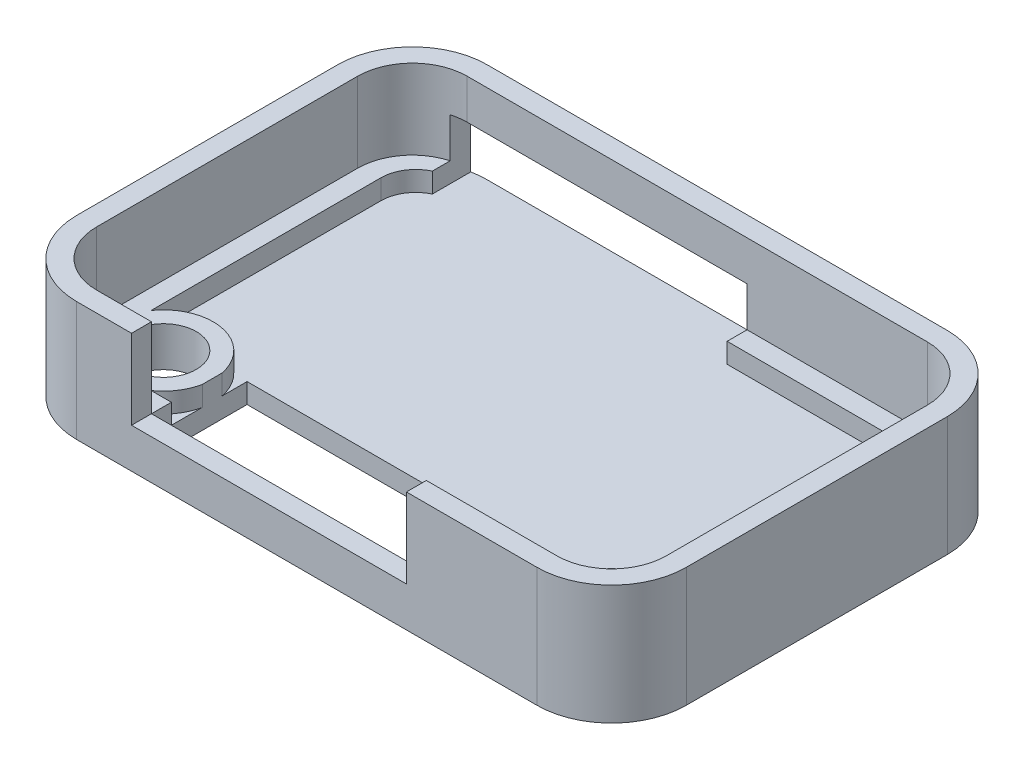
SolidWorks part; units mm, degrees
ref_plane "前视基准面" through (0, 0, 0) normal (0, 0, 1) x (1, 0, 0)
ref_plane "上视基准面" through (0, 0, 0) normal (0, 1, 0) x (1, 0, 0)
ref_plane "右视基准面" through (0, 0, 0) normal (1, 0, 0) x (0, 0, -1)
other "Configuration Table"
sketch "草图1" plane through (0, 0, 0) normal (0, 1, 0) x (1, 0, 0)
  line L1 (-15.3, 10.3) -> (15.3, 10.3)
  line L2 (-15.3, 10.3) -> (-15.3, -10.3)
  line L3 (-15.3, -10.3) -> (15.3, -10.3)
  line L4 (15.3, 10.3) -> (15.3, -10.3)
extrude "凸台-拉伸1" add sketch "草图1" along normal blind 6
sketch "草图2" plane through (0, 6, 0) normal (0, 1, 0) x (1, 0, 0)
  line L1 (-14.3, 9.3) -> (14.3, 9.3)
  line L2 (-14.3, 9.3) -> (-14.3, -9.3)
  line L3 (-14.3, -9.3) -> (14.3, -9.3)
  line L4 (14.3, 9.3) -> (14.3, -9.3)
extrude "切除-拉伸1" cut sketch "草图2" against normal blind 4
sketch "草图3" plane through (0, 2, 0) normal (0, 1, 0) x (1, 0, 0)
  line L1 (-13.3, 8.3) -> (13.3, 8.3)
  line L2 (-13.3, 8.3) -> (-13.3, -8.3)
  line L3 (-13.3, -8.3) -> (13.3, -8.3)
  line L4 (13.3, 8.3) -> (13.3, -8.3)
extrude "切除-拉伸2" cut sketch "草图3" against normal blind 1
fillet "圆角1" radius 2.75 4 edges at (-14.3, 4, 9.3) (14.3, 4, 9.3) (14.3, 4, -9.3) (-14.3, 4, -9.3)
fillet "圆角2" radius 3.75 4 edges at (-15.3, 3, -10.3) (-15.3, 3, 10.3) (15.3, 3, 10.3) (15.3, 3, -10.3)
sketch "草图4" plane through (0, 0, -10.3) normal (0, 0, -1) x (-1, 0, 0)
  line L1 (-2.5, 4) -> (12.3, 4)
  line L2 (-2.5, 4) -> (-2.5, 1)
  line L3 (-2.5, 1) -> (12.3, 1)
  line L4 (12.3, 4) -> (12.3, 1)
extrude "切除-拉伸3" cut sketch "草图4" against normal blind 5
fillet "圆角3" radius 1.75 4 edges at (-13.3, 1.5, 8.3) (13.3, 1.5, 8.3) (13.3, 1.5, -8.3) (-13.3, 1.5, -8.3)
sketch "草图5" plane through (0, 1, 0) normal (0, 1, 0) x (1, 0, 0)
  circle A0 centre (-11.25, -6.25) radius 2.5
  circle A1 centre (-11.25, -6.25) radius 1.65
  circle A2 centre (11.25, -6.25) radius 2.5
  circle A3 centre (11.25, -6.25) radius 1.65
extrude "凸台-拉伸2" add sketch "草图5" along normal blind 1
sketch "草图6" plane through (0, 1, 0) normal (0, 1, 0) x (1, 0, 0)
  circle A0 centre (-11.25, -6.25) radius 1.65
  circle A1 centre (11.25, -6.25) radius 1.65
extrude "切除-拉伸4" cut sketch "草图6" against normal blind 2
sketch "草图7" plane through (0, 6, 0) normal (0, 1, 0) x (1, 0, 0)
  line L1 (-8.8, -4.5) -> (5, -4.5)
  line L2 (-8.8, -4.5) -> (-8.8, -9.3)
  line L3 (-8.8, -9.3) -> (5, -9.3)
  line L4 (5, -4.5) -> (5, -9.3)
  line L5 (-11.55, -9.3) -> (11.55, -9.3) construction
  point P4 (-8.5771, -9.3)
  point P6 (0, 0)
  point P7 (-8.6343, -10.3)
extrude "切除-拉伸5" cut sketch "草图7" against normal blind 8
sketch "草图8" plane through (0, 0, 9.3) normal (0, 0, -1) x (-1, 0, 0)
  line L0 (11.55, 6) -> (-11.55, 6) construction
  line L1 (-5, 2) -> (8.8, 2)
  line L2 (-5, 2) -> (-5, 6)
  line L3 (-5, 6) -> (8.8, 6)
  line L4 (8.8, 2) -> (8.8, 6)
extrude "切除-拉伸6" cut sketch "草图8" against normal blind 10
